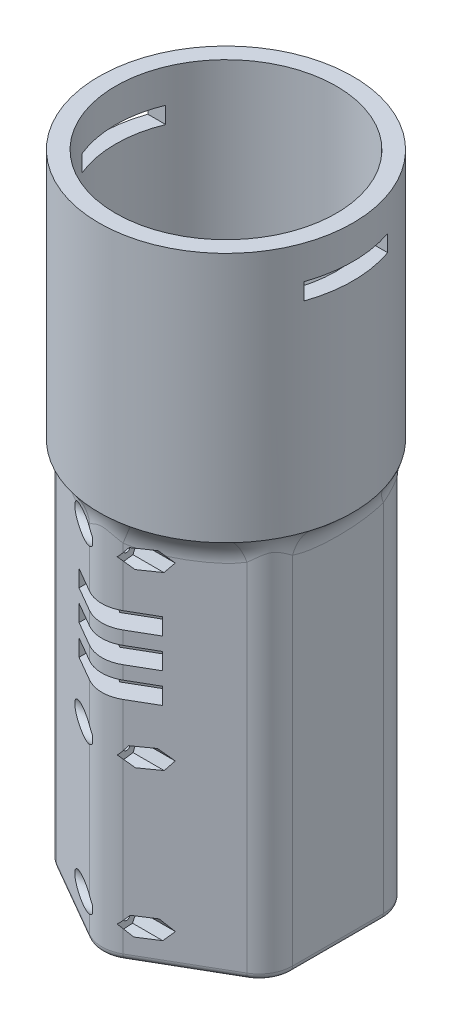
SolidWorks part; units mm, degrees
ref_plane "Front Plane" through (0, 0, 0) normal (0, 0, 1) x (1, 0, 0)
ref_plane "Top Plane" through (0, 0, 0) normal (0, 1, 0) x (1, 0, 0)
ref_plane "Right Plane" through (0, 0, 0) normal (1, 0, 0) x (0, 0, -1)
sketch "Sketch1" plane through (0, 0, 0) normal (0, 1, 0) x (1, 0, 0)
  line L1 (0, -31.7543) -> (27.5, -15.8771)
  line L2 (27.5, -15.8771) -> (27.5, 15.8771)
  line L3 (27.5, 15.8771) -> (0, 31.7543)
  line L4 (0, 31.7543) -> (-27.5, 15.8771)
  line L5 (-27.5, 15.8771) -> (-27.5, -15.8771)
  line L6 (-27.5, -15.8771) -> (0, -31.7543)
  line L7 (0, -38.6825) -> (33.5, -19.3412)
  line L8 (33.5, -19.3412) -> (33.5, 19.3412)
  line L9 (33.5, 19.3412) -> (0, 38.6825)
  line L10 (0, 38.6825) -> (-33.5, 19.3412)
  line L11 (-33.5, 19.3412) -> (-33.5, -19.3412)
  line L12 (-33.5, -19.3412) -> (0, -38.6825)
  circle A0 centre (0, 0) radius 27.5 construction
  circle A1 centre (0, 0) radius 33.5 construction
  dimension "D1" = 55
  dimension "D2" = 6
extrude "Boss-Extrude1" add sketch "Sketch1" along normal blind 110
fillet "Fillet1" radius 10 6 edges at (0, 55, 38.6825) (-33.5, 55, 19.3412) (-33.5, 55, -19.3412) (0, 55, -38.6825) (33.5, 55, -19.3412) (33.5, 55, 19.3412)
sketch "Sketch2" plane through (0, 110, 0) normal (0, 1, 0) x (1, 0, 0)
  circle A0 centre (0, 0) radius 33
  circle A1 centre (0, 0) radius 38
  dimension "D1" = 66
  dimension "D2" = 5
extrude "Boss-Extrude4" add sketch "Sketch2" along normal blind 75
sketch "Sketch3" plane through (0, 110, 0) normal (0, 1, 0) x (1, 0, 0)
  circle A0 centre (0, 0) radius 33
  circle A1 centre (0, 0) radius 20
  dimension "D1" = 40
extrude "Boss-Extrude5" add sketch "Sketch3" along normal blind 5
sketch "Sketch4" plane through (0, 115, 0) normal (0, 1, 0) x (1, 0, 0)
  circle A0 centre (-16, 16) radius 1
  circle A1 centre (16, 16) radius 1
  circle A2 centre (18.1101, -16) radius 1
  circle A3 centre (-16, -16) radius 1
  dimension "D1" = 2
  dimension "D2" = 2
  dimension "D3" = 2
  dimension "D4" = 2
  dimension "D5" = 32
  dimension "D6" = 32
  dimension "D7" = 32
  dimension "D8" = 16
  dimension "D9" = 16
  dimension "D10" = 16
extrude "Cut-Extrude1" cut sketch "Sketch4" against normal blind 5
sketch "Sketch5" plane through (0, 0, 0) normal (0, -1, 0) x (-1, 0, 0)
  line L7 (-5, 35.7957) -> (-28.5, 22.228)
  line L8 (-33.5, 13.5677) -> (-33.5, -13.5677)
  line L9 (-28.5, -22.228) -> (-5, -35.7957)
  line L10 (5, -35.7957) -> (28.5, -22.228)
  line L11 (33.5, -13.5677) -> (33.5, 13.5677)
  line L12 (28.5, 22.228) -> (5, 35.7957)
  circle A1 centre (0, 0) radius 33.5 construction
  arc A3 (33.5, 13.5677) -> (28.5, 22.228) centre (23.5, 13.5677) ccw
  arc A4 (-5, 35.7957) -> (5, 35.7957) centre (0, 27.1355) cw
  arc A5 (-28.5, 22.228) -> (-33.5, 13.5677) centre (-23.5, 13.5677) ccw
  arc A6 (-33.5, -13.5677) -> (-28.5, -22.228) centre (-23.5, -13.5677) ccw
  arc A7 (-5, -35.7957) -> (5, -35.7957) centre (0, -27.1355) ccw
  arc A8 (28.5, -22.228) -> (33.5, -13.5677) centre (23.5, -13.5677) ccw
  dimension "D3" = 10
  dimension "D1" = 67
extrude "Boss-Extrude6" add sketch "Sketch5" along normal blind 5
sketch "Sketch6" plane through (0, -5, 0) normal (0, -1, 0) x (1, 0, 0)
  line L5 (-0.8, -4.75) -> (0.8, -4.75)
  line L6 (-1.8, -3.75) -> (-1.8, 3.75)
  line L7 (-0.8, 4.75) -> (0.8, 4.75)
  line L8 (1.8, -3.75) -> (1.8, 3.75)
  line L9 (-1.8, -4.75) -> (1.8, 4.75) construction
  line L10 (-1.8, 4.75) -> (1.8, -4.75) construction
  arc A4 (0.8, -4.75) -> (1.8, -3.75) centre (0.8, -3.75) ccw
  arc A5 (0.8, 4.75) -> (1.8, 3.75) centre (0.8, 3.75) cw
  arc A6 (-1.8, 3.75) -> (-0.8, 4.75) centre (-0.8, 3.75) cw
  arc A7 (-0.8, -4.75) -> (-1.8, -3.75) centre (-0.8, -3.75) cw
  point P0 (0, 0)
  dimension "D3" = 1
  dimension "D1" = 9.5
  dimension "D2" = 3.6
extrude "Cut-Extrude2" cut sketch "Sketch6" against normal blind 5
sketch "Sketch8" plane through (-33.5, 0, 0) normal (-1, 0, 0) x (0, 0, 1)
  line L0 (-13.5677, 110) -> (-13.5677, -5) construction
  line L1 (-6.8277, 20) -> (5.6723, 20)
  line L2 (-6.8277, 20) -> (-6.8277, 0)
  line L3 (-6.8277, 0) -> (5.6723, 0)
  line L4 (5.6723, 20) -> (5.6723, 0)
  line L5 (-6.8277, 20) -> (5.6723, 0) construction
  line L6 (-6.8277, 0) -> (5.6723, 20) construction
  line L7 (13.5677, -5) -> (13.5677, 110) construction
  line L8 (13.5677, -5) -> (-13.5677, -5) construction
  line L9 (-10.8277, 99) -> (9.6723, 99)
  line L10 (-10.8277, 99) -> (-10.8277, 55)
  line L11 (-10.8277, 55) -> (9.6723, 55)
  line L12 (9.6723, 99) -> (9.6723, 55)
  line L13 (-10.8277, 99) -> (9.6723, 55) construction
  line L14 (-10.8277, 55) -> (9.6723, 99) construction
  circle A0 centre (-0.0004, 37.5) radius 6
  point P0 (-0.5777, 10)
  point P9 (-0.5777, 77)
  dimension "D11" = 12
  dimension "D1" = 12.5
  dimension "D2" = 6.74
  dimension "D3" = 20
  dimension "D4" = 7.8955
  dimension "D5" = 44
  dimension "D6" = 20.5
  dimension "D7" = 2.74
  dimension "D8" = 3.8955
  dimension "D9" = 35
  dimension "D10" = 5
  dimension "D12" = 17.5
extrude "Cut-Extrude3" cut sketch "Sketch8" against normal blind 5
fillet "Fillet2" radius 10 12 edges at (0, 110, -37.1355) (16.75, 110, -29.0119) (32.1603, 110, -18.5677) (33.5, 110, 0) (32.1603, 110, 18.5677) (16.75, 110, 29.0119) (0, 110, 37.1355) (-16.75, 110, 29.0119) (-32.1603, 110, 18.5677) (-33.5, 110, 0) (-32.1603, 110, -18.5677) (-16.75, 110, -29.0119)
sketch "Sketch9" plane through (-33.5, 0, 0) normal (-1, 0, 0) x (0, 0, 1)
  line L1 (-37.0736, 110) -> (-25.759, 110) construction
  line L3 (-22.228, -5) -> (-22.228, 103.4621) construction
  circle A0 centre (-33.228, 100) radius 1
  circle A1 centre (-33.228, 4.6647) radius 1
  circle A2 centre (-33.228, 48.6753) radius 1
  dimension "D1" = 2
  dimension "D2" = 2
  dimension "D3" = 2
  dimension "D4" = 10
  dimension "D5" = 10
  dimension "D6" = 11
  dimension "D7" = 11
  dimension "D8" = 11
extrude "Cut-Extrude4" cut sketch "Sketch9" against normal blind 40
sketch "Sketch10" plane through (33.5, 0, 0) normal (1, 0, 0) x (0, 0, -1)
  line L1 (34.4718, 97.0783) -> (36.3802, 99.6164)
  line L2 (36.3802, 99.6164) -> (35.1363, 102.538)
  line L3 (35.1363, 102.538) -> (31.9841, 102.9217)
  line L4 (31.9841, 102.9217) -> (30.0758, 100.3836)
  line L5 (30.0758, 100.3836) -> (31.3197, 97.462)
  line L6 (31.3197, 97.462) -> (34.4718, 97.0783)
  line L7 (34.4382, 45.7395) -> (36.3755, 48.2555)
  line L8 (36.3755, 48.2555) -> (35.1653, 51.1912)
  line L9 (35.1653, 51.1912) -> (32.0178, 51.6111)
  line L10 (32.0178, 51.6111) -> (30.0804, 49.0951)
  line L11 (30.0804, 49.0951) -> (31.2906, 46.1593)
  line L12 (31.2906, 46.1593) -> (34.4382, 45.7395)
  line L13 (34.6164, 1.8089) -> (36.3954, 4.4392)
  line L14 (36.3954, 4.4392) -> (35.007, 7.295)
  line L15 (35.007, 7.295) -> (31.8396, 7.5205)
  line L16 (31.8396, 7.5205) -> (30.0606, 4.8903)
  line L17 (30.0606, 4.8903) -> (31.4489, 2.0344)
  line L18 (31.4489, 2.0344) -> (34.6164, 1.8089)
  circle A0 centre (33.228, 100) radius 2.75 construction
  circle A1 centre (33.228, 48.6753) radius 2.75 construction
  circle A2 centre (33.228, 4.6647) radius 2.75 construction
  dimension "D1" = 5.5
  dimension "D2" = 5.5
  dimension "D3" = 5.5
extrude "Cut-Extrude5" cut sketch "Sketch10" against normal blind 30
sketch "Sketch11" plane through (-33.5, 0, 0) normal (-1, 0, 0) x (0, 0, 1)
  circle A0 centre (-33.228, 100) radius 3.5
  circle A1 centre (-33.228, 48.6753) radius 3.5
  circle A2 centre (-33.228, 4.6647) radius 3.5
  dimension "D1" = 7
  dimension "D2" = 7
  dimension "D3" = 7
extrude "Cut-Extrude6" cut sketch "Sketch11" against normal blind 30
mirror "Mirror2" about plane through (0, 0, 0) normal (0, 0, 1) of "Cut-Extrude6", "Cut-Extrude5", "Cut-Extrude4"
sketch "Sketch14" plane through (-33.5, 0, 0) normal (-1, 0, 0) x (0, 0, 1)
  line L0 (33, 185) -> (-33, 185) construction
  line L1 (-12.5, 175) -> (12.5, 175)
  line L2 (-12.5, 175) -> (-12.5, 170)
  line L3 (-12.5, 170) -> (12.5, 170)
  line L4 (12.5, 175) -> (12.5, 170)
  line L5 (-12.5, 175) -> (12.5, 170) construction
  line L6 (-12.5, 170) -> (12.5, 175) construction
  point P0 (0, 172.5)
  dimension "D1" = 5
  dimension "D2" = 25
  dimension "D3" = 12.5
  dimension "D4" = 10
extrude "Cut-Extrude8" cut sketch "Sketch14" against normal through all both and the other way through all
sketch "Sketch15" plane through (0, 0, 0) normal (0, 0, 1) x (1, 0, 0)
  line L0 (5, 98.8391) -> (5, 49.662) construction
  line L1 (-12.5, 85.95) -> (12.5, 85.95)
  line L2 (-12.5, 85.95) -> (-12.5, 80.95)
  line L3 (-12.5, 80.95) -> (12.5, 80.95)
  line L4 (12.5, 85.95) -> (12.5, 80.95)
  line L5 (-12.5, 85.95) -> (12.5, 80.95) construction
  line L6 (-12.5, 80.95) -> (12.5, 85.95) construction
  line L7 (-12.5, 76.95) -> (12.5, 76.95)
  line L8 (-12.5, 76.95) -> (-12.5, 71.95)
  line L9 (-12.5, 71.95) -> (12.5, 71.95)
  line L10 (12.5, 76.95) -> (12.5, 71.95)
  line L11 (-12.5, 76.95) -> (12.5, 71.95) construction
  line L12 (-12.5, 71.95) -> (12.5, 76.95) construction
  line L13 (-12.5, 67.95) -> (12.5, 67.95)
  line L14 (-12.5, 67.95) -> (-12.5, 62.95)
  line L15 (-12.5, 62.95) -> (12.5, 62.95)
  line L16 (12.5, 67.95) -> (12.5, 62.95)
  line L17 (-12.5, 67.95) -> (12.5, 62.95) construction
  line L18 (-12.5, 62.95) -> (12.5, 67.95) construction
  point P0 (0, 83.45)
  point P5 (0, 74.45)
  point P10 (0, 65.45)
  dimension "D1" = 5
  dimension "D2" = 4
  dimension "D3" = 4
  dimension "D4" = 5
  dimension "D5" = 5
  dimension "D6" = 25
  dimension "D7" = 25
  dimension "D8" = 25
  dimension "D9" = 5
extrude "Cut-Extrude9" cut sketch "Sketch15" against normal through all both and the other way through all
sketch "Sketch16" plane through (0, 115, 0) normal (0, 1, 0) x (1, 0, 0)
  circle A0 centre (-27, 0) radius 4
  circle A1 centre (0, 27) radius 4
  circle A2 centre (27, 0) radius 4
  circle A3 centre (0, -27) radius 4
  circle A11 centre (0, 0) radius 33 construction
  circle A13 centre (0, 0) radius 33 construction
  dimension "D1" = 8
  dimension "D2" = 8
  dimension "D3" = 8
  dimension "D4" = 8
  dimension "D8" = 6
  dimension "D5" = 6
  dimension "D6" = 6
  dimension "D7" = 6
extrude "Cut-Extrude10" cut sketch "Sketch16" against normal blind 10
fillet "Fillet3" radius 2 12 edges at (32.1603, -5, -18.5677) (16.75, -5, -29.0119) (0, -5, -37.1355) (-16.75, -5, -29.0119) (-32.1603, -5, -18.5677) (-33.5, -5, 0) (-32.1603, -5, 18.5677) (-16.75, -5, 29.0119) (0, -5, 37.1355) (16.75, -5, 29.0119) (32.1603, -5, 18.5677) (33.5, -5, 0)
